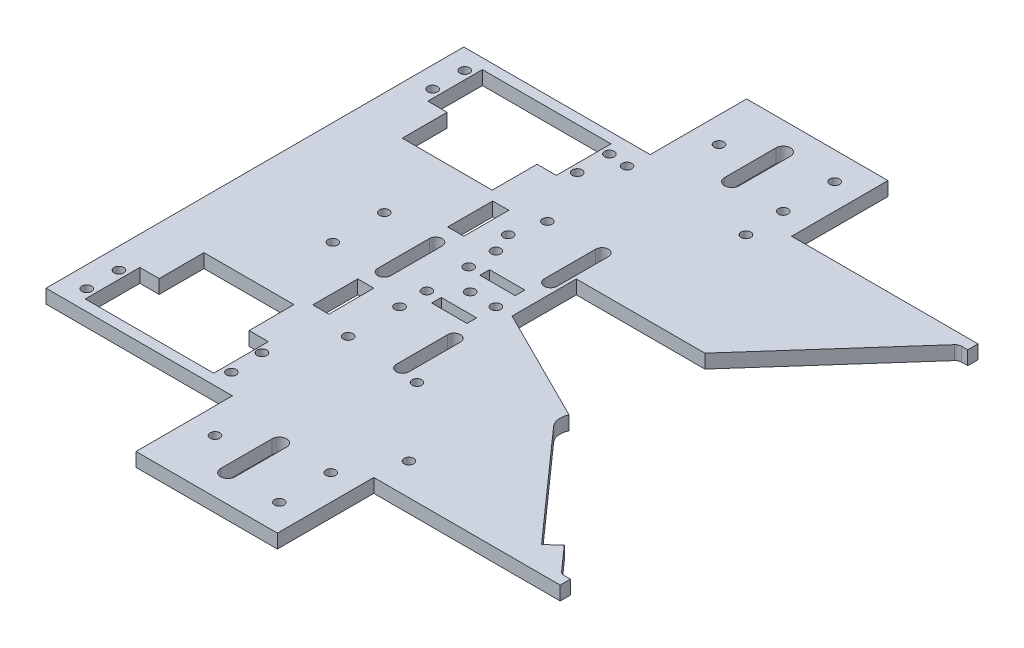
SolidWorks part; units mm, degrees
ref_plane "Front Plane" through (0, 0, 0) normal (0, 0, 1) x (1, 0, 0)
ref_plane "Top Plane" through (0, 0, 0) normal (0, 1, 0) x (1, 0, 0)
ref_plane "Right Plane" through (0, 0, 0) normal (1, 0, 0) x (0, 0, -1)
sketch "Sketch2" plane through (0, 0, 0) normal (0, 1, 0) x (1, 0, 0)
  line L2 (0, 0) -> (0, 65)
  line L3 (0, 65) -> (58, 65)
  line L4 (160, 0) -> (160, 65)
  line L8 (0, 0) -> (160, 0)
  line L9 (102, 65) -> (160, 65)
  line L11 (102, 65) -> (102, 95)
  line L12 (58, 65) -> (58, 95)
  line L13 (58, 95) -> (102, 95)
  dimension "D1" = 65
  dimension "D2" = 160
  dimension "D3" = 44
  dimension "D4" = 30
extrude "Boss-Extrude1" add sketch "Sketch2" along normal blind 4.3
mirror "Mirror1" about plane through (0, 4.3, 0) normal (0, 0, -1) of bodies 101
sketch "Sketch3" plane through (0, 4.3, 0) normal (0, 1, 0) x (1, 0, 0)
  line L0 (160, 61.8) -> (160, -61.8)
  line L1 (120.0126, 20) -> (157.1565, 61.8)
  line L3 (80.0126, 0) -> (80.0126, 20)
  line L4 (80.0126, 20) -> (120.0126, 20)
  line L12 (160, 65) -> (102, 65)
  line L13 (102, 65) -> (102, 95)
  line L15 (102, 95) -> (58, 95)
  line L16 (58, 65) -> (0, 65)
  line L17 (0, 65) -> (0, -65)
  line L18 (0, -65) -> (58, -65)
  line L20 (58, 95) -> (58, 65)
  line L22 (102, -65) -> (160, -65)
  line L23 (160, -65) -> (160, 65)
  line L36 (58, -65) -> (58, -95)
  line L38 (58, -95) -> (102, -95)
  line L39 (58, -95) -> (102, -95)
  line L40 (102, -95) -> (102, -65)
  line L42 (160, -61.8) -> (157.1556, -61.8)
  line L45 (160, 61.8) -> (157.1565, 61.8)
  line L48 (80.0126, 0) -> (120, -20)
  line L49 (120, -20) -> (157.1556, -61.8)
  line M24 (160, -65) -> (160, 65)
  dimension "D2" = 130
  dimension "D3" = 20
  dimension "D4" = 40
  dimension "D1" = 0
extrude "Cut-Extrude1" cut sketch "Sketch3" against normal blind 4.5 contours L48 L49 L1 L4 L3 M24 region at (132.7054, 4.3, -1.1594)
fillet "Fillet1" radius 2 2 edges at (157.1565, 2.15, -61.8) (157.1556, 2.15, 61.8)
ref_axis "Axis1" through (80, 4.3, 95) along (0, 0, -1)
sketch "Sketch4" plane through (0, 4.3, 0) normal (0, 1, 0) x (1, 0, 0)
  line L0 (80, -95) -> (80, 95)
  line L1 (102, -95) -> (58, -95) construction
  line L2 (102, 95) -> (58, 95) construction
ref_plane "Plane2" through (0, 4.3, 0) normal (0, 1, 0) x (1, 0, 0)
sketch "Sketch6" plane through (0, 4.3, 0) normal (0, 1, 0) x (1, 0, 0)
  line L3 (9, -61.8) -> (49, -61.8)
  line L6 (29, -45.8) -> (29, -44.8)
  line L7 (9, -44.8) -> (15, -44.8)
  line L11 (43, -44.8) -> (43, -30.8418)
  line L12 (15, -44.8) -> (15, -30.8418)
  line L13 (15, -30.8418) -> (43, -30.8418)
  line L15 (0, 0) -> (80.0126, 0)
  line L16 (80.0126, 0) -> (120, -20) construction
  line L18 (9, 44.8) -> (15, 44.8)
  line L20 (15, 30.8418) -> (43, 30.8418)
  line L21 (15, 44.8) -> (15, 30.8418)
  line L22 (43, 44.8) -> (43, 30.8418)
  line L25 (15, -45.8) -> (15, -30.8418) construction
  line L27 (9, 61.8) -> (49, 61.8)
  line L30 (4, -61.8) -> (3, -61.8)
  line L31 (0, -61.8) -> (160, -61.8) construction
  line L32 (3, -61.8) -> (4, -61.8)
  line L33 (3, -44.8) -> (3, -62.8) construction
  line L34 (3, -62.8) -> (55, -62.8) construction
  line L35 (55, -44.8) -> (55, -62.8) construction
  line L36 (4, -61.8) -> (54, -61.8) construction
  line L37 (0, 61.8) -> (160, 61.8) construction
  line L38 (54, 61.8) -> (55, 61.8)
  line L39 (54, 61.8) -> (55, 61.8)
  line L40 (43, 44.8) -> (49, 44.8)
  line L41 (4, -45.8) -> (4, -61.8) construction
  line L42 (4, -45.8) -> (54, -45.8) construction
  line L43 (43, -44.8) -> (49, -44.8)
  line L44 (3, -44.8) -> (55, -44.8) construction
  line L45 (29, -45.8) -> (29, -30.8418) construction
  line L46 (43, -45.8) -> (43, -30.8418) construction
  line L47 (54, -45.8) -> (54, -61.8) construction
  line L48 (9, -61.8) -> (49, -61.8)
  line L52 (9, 61.8) -> (9, 44.8)
  line L53 (55, 61.8) -> (54, 61.8)
  line L56 (49, 61.8) -> (49, 44.8)
  line L59 (3, -61.8) -> (4, -61.8)
  line L60 (9, -44.8) -> (9, -61.8)
  line L64 (49, -44.8) -> (49, -61.8)
  dimension "D4" = 1
  dimension "D5" = 14
  dimension "D6" = 14
extrude "Cut-Extrude2" cut sketch "Sketch6" against normal blind 10
sketch "Sketch8" plane through (0, 4.3, 0) normal (0, 1, 0) x (1, 0, 0)
  circle A0 centre (6.5, 58.8) radius 1.5
  circle A1 centre (6.5, 48.8) radius 1.5
  circle A2 centre (51.5, 48.8) radius 1.5
  circle A3 centre (51.5, 58.8) radius 1.5
  circle A4 centre (6.5, -48.8) radius 1.5
  circle A5 centre (6.5, -58.8) radius 1.5
  circle A6 centre (51.5, -58.8) radius 1.5
  circle A7 centre (51, -48.8) radius 1.5
  dimension "D7" = 3
extrude "Cut-Extrude3" cut sketch "Sketch8" against normal blind 10
sketch "Sketch9" plane through (0, 0, 0) normal (0, -1, 0) x (1, 0, 0)
  line L0 (75.75, 70.4) -> (75.75, 86.4)
  line L1 (75.75, -86.4) -> (75.75, -70.4)
  line L2 (80.25, -86.4) -> (80.25, -70.4)
  line L4 (80.25, 70.4) -> (80.25, 86.4)
  circle A0 centre (94, 70.4) radius 1.5
  circle A1 centre (66, 78.4) radius 1.5
  circle A2 centre (66, -78.4) radius 1.5
  circle A3 centre (94, -86.4) radius 1.5
  circle A4 centre (94, 86.4) radius 1.5
  circle A5 centre (94, -70.4) radius 1.5
  arc A6 (75.75, -86.4) -> (80.25, -86.4) centre (78, -86.4) ccw
  arc A7 (80.25, -70.4) -> (75.75, -70.4) centre (78, -70.4) ccw
  arc A10 (75.75, 70.4) -> (80.25, 70.4) centre (78, 70.4) ccw
  arc A12 (80.25, 86.4) -> (75.75, 86.4) centre (78, 86.4) ccw
  dimension "D1" = 3
extrude "Cut-Extrude4" cut sketch "Sketch9" against normal blind 10
sketch "Sketch7" plane through (0, 4.3, 0) normal (0, 1, 0) x (1, 0, 0)
  line L0 (0, 0) -> (80.0126, 0)
  line L1 (0, 65) -> (0, -65) construction
  line L2 (80.0126, 0) -> (80.0126, 20) construction
  line L3 (80, -95) -> (80, 95) construction
  line L4 (64, -9) -> (75, -9)
  line L5 (64, -6) -> (75, -6)
  line L6 (64, -9) -> (64, -6)
  line L7 (75, -9) -> (75, -6)
  line L8 (64, -7.5) -> (75, -7.5)
  line L9 (64, 7.5) -> (75, 7.5)
  line L10 (75, 9) -> (75, 6)
  line L11 (64, 9) -> (64, 6)
  line L12 (64, 6) -> (75, 6)
  line L13 (64, 9) -> (75, 9)
  circle A0 centre (60.0126, -6.5) radius 1.5
  circle A1 centre (60.0126, 6.5) radius 1.5
  dimension "D1" = 3
  dimension "D2" = 6.5
  dimension "D3" = 20
  dimension "D6" = 11
  dimension "D4" = 5
  dimension "D5" = 3
  dimension "D7" = 7.5
sketch "Sketch10" plane through (0, 4.3, 0) normal (0, 1, 0) x (1, 0, 0)
  line L0 (120, -20) -> (156.5589, -61.1287) construction
  line L1 (123.3218, -23.737) -> (149.8964, -53.6334)
  line L2 (116.263, -23.3218) -> (146.1593, -56.9552)
  line L3 (149.8964, -53.6334) -> (146.1593, -56.9552)
  line L4 (120, -20) -> (156.5589, -61.1287) construction
  line L5 (116.263, -23.3218) -> (152.8218, -64.4505) construction
  arc A0 (123.3218, -23.737) -> (116.263, -23.3218) centre (120, -20) ccw
  dimension "D1" = 5
  dimension "D2" = 45
extrude "Cut-Extrude5" cut sketch "Sketch10" against normal blind 10
sketch "Sketch11" plane through (0, 0, 0) normal (0, -1, 0) x (1, 0, 0)
  line L0 (0, 0) -> (80.0126, 0) construction
  line L1 (80, 95) -> (80, -95) construction
  line L2 (80.0126, 0) -> (0, 0)
  line L4 (75, 31.0313) -> (75, 15.0313)
  line L6 (79, 31.0313) -> (79, 15.0313)
  line L7 (79, -31.0313) -> (79, -15.0313)
  line L8 (75, -31.0313) -> (75, -15.0313)
  circle A0 centre (60, 31) radius 1.5
  circle A1 centre (60, 15) radius 1.5
  arc A2 (75, 31.0313) -> (79, 31.0313) centre (77, 31.0313) cw
  arc A3 (75, 15.0313) -> (79, 15.0313) centre (77, 15.0313) ccw
  arc A4 (75, -15.0313) -> (79, -15.0313) centre (77, -15.0313) cw
  arc A5 (75, -31.0313) -> (79, -31.0313) centre (77, -31.0313) ccw
  circle A6 centre (60, -15) radius 1.5
  circle A7 centre (60, -31) radius 1.5
  dimension "D1" = 3
  dimension "D2" = 16
  dimension "D3" = 15
  dimension "D4" = 20
  dimension "D5" = 15
  dimension "D6" = 4
extrude "Cut-Extrude6" cut sketch "Sketch11" against normal blind 10 contours L4 A3 L6 A2 | L8 A5 L7 A4 | A7 | A0 | A1 | A6 region at (77, 0, 23.0313) region at (77, 0, -23.0313) region at (60, 0, -31)
sketch "Sketch12" plane through (0, 0, 0) normal (0, -1, 0) x (-1, 0, 0)
  line L0 (0, 0) -> (-80.0126, 0) construction
  line L3 (-50.2627, -8) -> (-50.2627, 8)
  line L4 (-50.2627, 0) -> (-46.2627, 0)
  line L5 (-46.2627, -8) -> (-46.2627, 8)
  line L6 (0, 0) -> (-46.2627, 0)
  line L7 (0, 65) -> (0, -65) construction
  line L8 (-160, -61.8) -> (0, -61.8) construction
  line L9 (-80.0126, 0) -> (-50.2627, 0)
  line L10 (-80.0126, 0) -> (-115.5281, -17.7634) construction
  line L11 (-80.0126, 0) -> (-80.0126, 20) construction
  line L12 (-58, -65) -> (0, -65) construction
  line L13 (-58, 65) -> (0, 65) construction
  circle A0 centre (-32.2627, -8) radius 1.5
  circle A1 centre (-32.2627, 8) radius 1.5
  arc A2 (-46.2627, 8) -> (-50.2627, 8) centre (-48.2627, 8) ccw
  arc A3 (-50.2627, -8) -> (-46.2627, -8) centre (-48.2627, -8) ccw
  circle A5 centre (-32.2627, -8) radius 1.5 construction
  circle A6 centre (-32.2627, 8) radius 1.5 construction
  dimension "D1" = 3
  dimension "D8" = 8
  dimension "D9" = 8
  dimension "D2" = 8
  dimension "D3" = 14
  dimension "D4" = 4
  dimension "D5" = 61.8
  dimension "D6" = 65
  dimension "D7" = 65
extrude "Cut-Extrude7" cut sketch "Sketch12" against normal blind 10 contours A3 L5 L4 L3 | L4 L5 A2 L3 | A0 | A1 region at (48.2627, 0, 4.7958) region at (48.2627, 0, -4.7958) region at (32.2627, 0, 8) region at (32.2627, 0, -8)
extrude "Cut-Extrude8" cut sketch "Sketch7" against normal blind 9 contours A0 | L4 L7 L5 L6 | L12 L10 L13 L11 | A1
sketch "Sketch13" plane through (0, 4.3, 0) normal (0, 1, 0) x (1, 0, 0)
  line L0 (80.0126, 0) -> (59.0194, 0)
  line L1 (80, -95) -> (80, 95) construction
  circle A0 centre (67, 0) radius 1.5
  circle A1 centre (75, 0) radius 1.5
  dimension "D2" = 3
  dimension "D3" = 5
  dimension "D1" = 8
extrude "Cut-Extrude9" cut sketch "Sketch13" against normal blind 10 contours L0 A0 | L0 A0 | L0 A1 | L0 A1 region at (75, 4.3, 0.6366) region at (75, 4.3, -0.6366) region at (67, 4.3, 0.6366) region at (67, 4.3, -0.6366)
sketch "Sketch14" plane through (0, 4.3, 0) normal (0, 1, 0) x (1, 0, 0)
  circle A0 centre (57.5, 58.3) radius 1.5
  circle A1 centre (94.5, 58.3) radius 1.5
  circle A2 centre (57.5, 21.3) radius 1.5
  circle A3 centre (83.1278, -32.706) radius 1.5
  circle A4 centre (103.0587, -55.1282) radius 1.5
  dimension "D1" = 3
  dimension "D2" = 3
extrude "Cut-Extrude10" cut sketch "Sketch14" against normal blind 10
sketch "Sketch15" plane through (0, 4.3, 0) normal (0, 1, 0) x (1, 0, 0)
  line L1 (46, 28) -> (51, 28)
  line L2 (46, 28) -> (46, 14)
  line L3 (46, 14) -> (51, 14)
  line L4 (51, 28) -> (51, 14)
  line L6 (0, 65) -> (0, -65) construction
  line L7 (80.0126, 0) -> (53.7017, 0)
  line L8 (46, -14) -> (51, -14)
  line L9 (51, -28) -> (51, -14)
  line L10 (46, -28) -> (51, -28)
  line L11 (46, -28) -> (46, -14)
  arc A0 (50.2627, 8) -> (46.2627, 8) centre (48.2627, 8) ccw construction
  arc A1 (46.2627, -8) -> (50.2627, -8) centre (48.2627, -8) ccw construction
  dimension "D1" = 46
  dimension "D2" = 5
  dimension "D3" = 14
  dimension "D4" = 14
  dimension "D5" = 14
  dimension "D6" = 6
  dimension "D7" = 6
extrude "Cut-Extrude11" cut sketch "Sketch15" against normal blind 10 contours L4 L1 L2 L3 | L11 L10 L9 L8 region at (48.5, 4.3, -21) region at (48.5, 4.3, 21)
